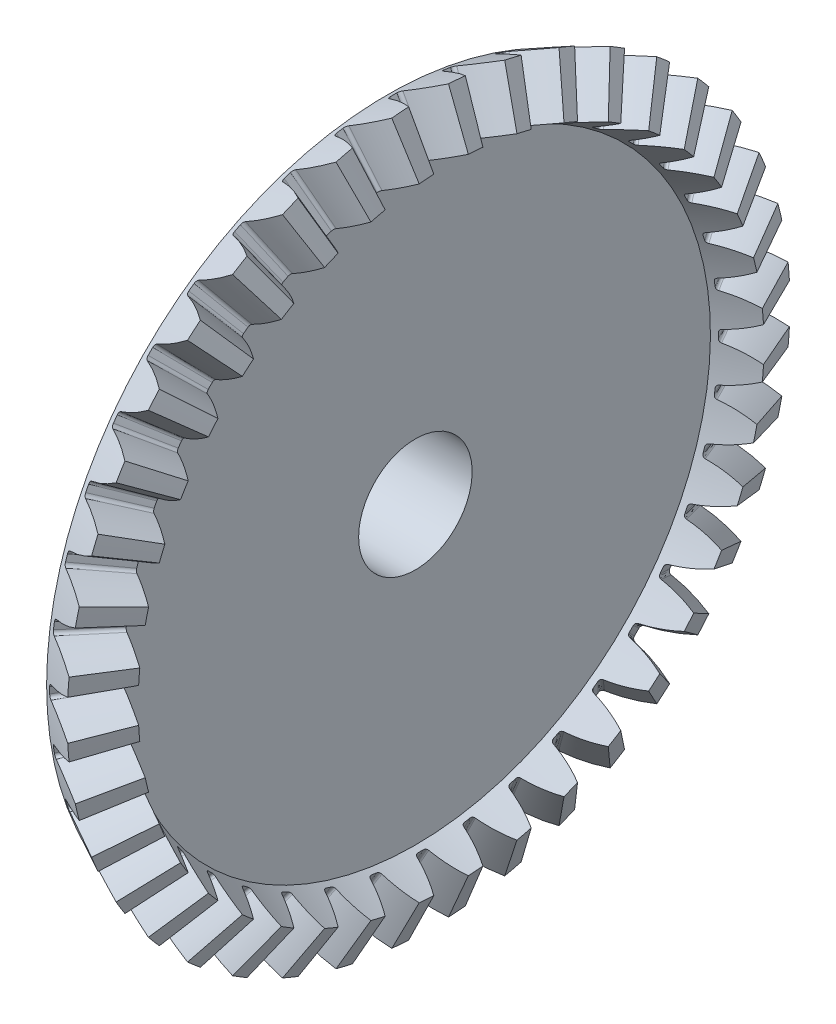
SolidWorks part; units mm, degrees
revolve "Base-Revolve" add sketch "BasProSke" angle 360 about L0 other way angle 4.5
sketch "BasProSke" plane through (0, 0, 0) normal (0, 1, 0) x (1, 0, 0)
  line L0 (-10, 0) -> (60, 0) construction
  line L1 (0, 0) -> (0, 81.0104)
  line L2 (0, 0) -> (6.6607, 0)
  line L3 (6.6607, 0) -> (6.6607, 70.1417)
  line L4 (49.6458, 0) -> (-6.8684, 113.0285) construction
  line L5 (0, 81.0104) -> (9.7926, 85.9067)
  line L6 (49.6458, 0) -> (-8.8085, 126.0029) construction
  line L7 (49.6458, 0) -> (0, 81.0104) construction
  line L8 (9.7926, 85.9067) -> (15.1395, 74.3811)
  line L9 (15.1395, 74.3811) -> (6.6607, 70.1417)
  line L10 (7.3125, 84.6667) -> (-4.6718, 84.6667) construction
  dimension "D4" = 1.678
ref_plane "Plane1" through (0, 0, 0) normal (0, 0, 1) x (1, 0, 0)
ref_plane "Plane2" through (0, 0, 0) normal (0, 1, 0) x (1, 0, 0)
ref_plane "Plane3" through (0, 0, 0) normal (1, 0, 0) x (0, 0, -1)
sketch "HoldingSke" plane through (0, 0, 0) normal (0, 1, 0) x (1, 0, 0)
  line L0 (0, 0) -> (116.7452, -97.9608)
  line L1 (-15, 0) -> (100, 0) construction
  line L2 (0, 0) -> (-75.7593, 24.4387)
  line L3 (0, 0) -> (-11.863, 4.5341)
  line L4 (0, 0) -> (6.6156, 5.5511)
  line L5 (0, 0) -> (-66.6361, -24.8533)
  line L6 (0, 0) -> (-10.5278, -7.1032)
  line L7 (-75.7593, 24.4387) -> (-65.3329, 94.7903)
  line L8 (-76.2, 54.61) -> (-46.2788, 54.61)
  line L9 (-71.009, 38.7566) -> (-53.1078, 45.2721)
  line L10 (-76.2, 71.12) -> (104.1128, 71.12)
  line L11 (0, 0) -> (-12.7, 0)
  line L12 (-76.2, 101.6) -> (-76.0298, 101.6)
  line L13 (24.9733, 27.94) -> (52.9543, 28.2599)
  line L14 (24.9733, 27.94) -> (25.0241, 27.9398)
  line L15 (24.9733, 27.94) -> (100.3916, 29.9584)
  line L16 (-75.7593, 24.4387) -> (45.5619, -19.7186)
  circle A0 centre (0, 0) radius 13.4938
  circle A1 centre (0, 0) radius 19.05
  circle A2 centre (0, 0) radius 19.05
  circle A3 centre (0, 0) radius 13.4938
  dimension "Num_teeth" = 40
  dimension "Pitch_radius" = 180.3128
  dimension "Width" = 12.7
ref_plane "ToothPln" through (4.8963, 83.4586, 0) normal (-0.4472, 0.8944, 0) x (0, 0, -1)
ref_plane "ToothPln2" through (9.9292, -19.8583, 0) normal (-0.4472, 0.8944, 0) x (0, 0, 1)
sketch "TooCutSke" plane through (4.8963, 83.4586, 0) normal (-0.4472, 0.8944, 0) x (0, 0, -1)
  line L2 (0, 81.9653) -> (136.6289, -1654.0695) construction
  line L3 (0, 81.9653) -> (74.2212, -1759.8687) construction
  line L4 (0, -15.621) -> (0, 105.791) construction
  line L6 (-24.765, -5.4742) -> (21.082, -5.4742) construction
  line L7 (6.6429, -2.4404) -> (3.4066, -2.5708) construction
  arc A0 (-5.6568, -7.0434) -> (5.6568, -7.0434) centre (0, 81.9653) ccw
  arc A1 (-0.7735, 3.8429) -> (0.7735, 3.8429) centre (0, 81.9653) ccw
  circle A2 centre (0, 81.9653) radius 84.6667 construction
  circle A3 centre (0, 81.9653) radius 79.5606 construction
  arc A4 (1.6092, 3.1762) -> (0.7735, 3.8429) centre (0.7818, 2.9963) ccw
  arc A5 (1.6092, 3.1762) -> (5.6568, -7.0434) centre (34.7026, 10.3718) ccw
  arc A6 (-5.6568, -7.0434) -> (-1.6092, 3.1762) centre (-34.7026, 10.3718) ccw
  arc A7 (-0.7735, 3.8429) -> (-1.6092, 3.1762) centre (-0.7818, 2.9963) ccw
  ellipse E0 centre (0, 32.9444) end of major axis (85.9067, 32.9444) minor radius 38.4187 construction
sketch "TooCutSke2" plane through (9.9292, -19.8583, 0) normal (-0.4472, 0.8944, 0) x (0, 0, 1)
  line L0 (0, 0) -> (0, 68.072) construction
  line L2 (21.082, 36.229) -> (-20.32, 36.229) construction
  circle A0 centre (0, 44.4046) radius 0.0127
  ellipse E1 centre (0, 0) end of major axis (-81.0104, 0) minor radius 36.229 construction
loft "ToothCut" cut profiles "TooCutSke2", "TooCutSke"
pattern_circular "TeethCuts" count 40 every 9 about axis through (-10, 0, 0) along (1, 0, 0) of "ToothCut"
sketch "HubSke" plane through (0, 0, 0) normal (-1, 0, 0) x (0, 0, 1)
  circle A0 centre (0, 0) radius 19.05
  dimension "Diameter" = 38.1
extrude "Hub" add sketch "HubSke" along normal blind 21.4743
sketch "BorSke" plane through (0, 0, 0) normal (1, 0, 0) x (0, 0, -1)
  circle A0 centre (0, 0) radius 13.4938
  dimension "Diameter" = 26.9875
extrude "Bore" cut sketch "BorSke" along normal mid plane 142.2401
sketch "KeySke" plane through (0, 0, 0) normal (1, 0, 0) x (0, 0, -1)
  line L0 (-3.175, 0) -> (-3.175, 16.4274)
  line L1 (-3.175, 16.4274) -> (3.175, 16.4274)
  line L2 (3.175, 16.4274) -> (3.175, 0)
  line L3 (0, 0) -> (0, 34) construction
  line L4 (-3.175, 0) -> (3.175, 0)
extrude "Keyway" [suppressed] cut sketch "KeySke" along normal mid plane 142.2401
pattern_circular "Keyway2" [suppressed] count 2 every 90 about axis through (-10, 0, 0) along (1, 0, 0)
equation "' \"Pitch@HoldingSke\" = 4"
equation "' \"Num_teeth@HoldingSke\" = 20"
equation "' \"Mating_teeth@HoldingSke\" = 12"
equation "' \"Ap@HoldingSke\" =  20"
equation "' \"Ap@HoldingSke\" = 20"
equation "' \"Width@HoldingSke\" = 0.5"
equation "' \"Hub_dia@HoldingSke\"= 2"
equation "' \"Hub_dia@HoldingSke\" = 2"
equation "' \"Mounting_dist@HoldingSke\" = 3"
equation "' \"Bore@HoldingSke\" = 0.75"
equation "' \"T_dim@HoldingSke\" = 0.85"
equation "' \"Width@KeySke\" = 0.25"
equation "' \"Show_teeth@HoldingSke\" = 100"
equation "' \"Backlash@HoldingSke\" = 0.009"
equation "' \"Addendum_fac@HoldingSke\" = 1.0"
equation "' \"Dedendum_fac@HoldingSke\" = 1.188"
equation "' \"Dedendum_add@HoldingSke\" = 0.002"
equation "' \"Clearance_fac@HoldingSke\" = 0.188"
equation " \"Addendum_fac@HoldingSke\" = 0.54 + 0.46 / (\"Num_teeth@HoldingSke\" /  \"Mating_teeth@HoldingSke\" ) ^ 2"
equation "' \"Addendum_fac@HoldingSke\" = 2 - (0.54 + 0.46 / (\"Mating_teeth@HoldingSke\" /  \"Num_teeth@HoldingSke\" ) ^ 2)"
equation "\"Dedendum_fac@HoldingSke\" = 2.188 - \"Addendum_fac@HoldingSke\""
equation "\"Pitch_rad@BasProSke\" = \"Num_teeth@HoldingSke\" / \"Pitch@HoldingSke\" / 2"
equation "\"Pitch_ang@BasProSke\" = atn(\"Num_teeth@HoldingSke\" / \"Mating_teeth@HoldingSke\") * (180 / 3.14159265)"
equation "\"Addendum@BasProSke\" = \"Addendum_fac@HoldingSke\" / \"Pitch@HoldingSke\""
equation "\"Dedendum_plus@BasProSke\" = (\"Dedendum_fac@HoldingSke\" / \"Pitch@HoldingSke\" + \"Dedendum_add@HoldingSke\") * 1.25"
equation "\"Face_wid@BasProSke\" = \"Width@HoldingSke\""
equation "\"Radius@TooCutSke\" = ((\"Num_teeth@HoldingSke\" + 2 * \"Addendum_fac@HoldingSke\") / \"Pitch@HoldingSke\" ) / 2"
equation "\"Overcut_dia@TooCutSke\" =  1.02 * (\"Num_teeth@HoldingSke\" + 2 * \"Addendum_fac@HoldingSke\") / \"Pitch@HoldingSke\""
equation "\"Pitch_dia@TooCutSke\" = \"Num_teeth@HoldingSke\" / \"Pitch@HoldingSke\""
equation "\"Base_dia@TooCutSke\" = \"Num_teeth@HoldingSke\" / \"Pitch@HoldingSke\" * cos((\"Ap@HoldingSke\"  * 3.14159265 / 180))"
equation "'  \"Root_dia@TooCutSke\" =  (\"Num_teeth@HoldingSke\" + 2) / \"Pitch@HoldingSke\" - 2 * (\"Addendum_fac@HoldingSke\" + \"Dedendum_fac@HoldingSke\") / \"Pitch@HoldingSke\" - \"Dedendum_add@HoldingSke\" * 2"
equation "'  \"Root_dia@TooCutSke\" = (\"Num_teeth@HoldingSke\" + 2) / \"Pitch@HoldingSke\" - 2 * (\"Addendum_fac@HoldingSke\" + \"Dedendum_fac@HoldingSke\") / \"Pitch@HoldingSke\" - \"Dedendum_add@HoldingSke\" * 2"
equation "\"Root_dia@TooCutSke\" =  \"Num_teeth@HoldingSke\" / \"Pitch@HoldingSke\" - 2 * \"Dedendum_fac@HoldingSke\" / \"Pitch@HoldingSke\" - \"Dedendum_add@HoldingSke\" * 2"
equation "\"Half_ang@TooCutSke\" = 180 / \"Num_teeth@HoldingSke\""
equation "\"Half_CT@TooCutSke\" = \"Num_teeth@HoldingSke\" / \"Pitch@HoldingSke\" * sin((3.14159265 / 2 / \"Num_teeth@HoldingSke\")) / 2 - 2 * \"Backlash@HoldingSke\" / 4"
equation "\"Flank_rad@TooCutSke\" = \"Num_teeth@HoldingSke\" / \"Pitch@HoldingSke\" / 5"
equation "\"Root_fillet@TooCutSke\" = \"Clearance_fac@HoldingSke\" / \"Pitch@HoldingSke\" + \"Dedendum_add@HoldingSke\""
equation "\"Offset@ToothPln2\"  = \"Num_teeth@HoldingSke\" / \"Pitch@HoldingSke\" / 2 / sin(atn(\"Num_teeth@HoldingSke\" / \"Mating_teeth@HoldingSke\"))"
equation "\"Dedendum_plus@TooCutSke2\" = \"Dedendum_plus@BasProSke\""
equation "\"MHD@HoldingSke\" = \"Num_teeth@HoldingSke\" / \"Pitch@HoldingSke\" - 2 * \"Dedendum_plus@BasProSke\" * cos(atn(\"Num_teeth@HoldingSke\" / \"Mating_teeth@HoldingSke\"))"
equation "\"MBD@HoldingSke\" = \"Num_teeth@HoldingSke\" / \"Pitch@HoldingSke\" - 2 * \"Dedendum_plus@BasProSke\" * cos(atn(\"Num_teeth@HoldingSke\" / \"Mating_teeth@HoldingSke\")) - 0.002"
equation "\"MnMD@HoldingSke\" =  \"Num_teeth@HoldingSke\" / \"Pitch@HoldingSke\" / 2 / (\"Num_teeth@HoldingSke\" / \"Mating_teeth@HoldingSke\") + \"Dedendum_plus@BasProSke\" * sin(atn(\"Num_teeth@HoldingSke\" / \"Mating_teeth@HoldingSke\"))"
equation "\"OAL@HoldingSke\" = \"MnMD@HoldingSke\""
equation "\"MHD@HoldingSke\" = ((sgn( \"MHD@HoldingSke\" - \"Hub_dia@HoldingSke\" )-1)*( \"MHD@HoldingSke\" - \"Hub_dia@HoldingSke\" ))/-2+ \"Hub_dia@HoldingSke\""
equation "\"MBD@HoldingSke\" = ((sgn( \"MBD@HoldingSke\" - \"Bore@HoldingSke\" )-1)*( \"MBD@HoldingSke\" - \"Bore@HoldingSke\" ))/-2+ \"Bore@HoldingSke\""
equation "\"Face_wid@BasProSke\" = ((sgn( \"Face_wid@BasProSke\" - \"Offset@ToothPln2\" * 0.9)-1)*( \"Face_wid@BasProSke\" - \"Offset@ToothPln2\" * 0.9))/-2+ \"Offset@ToothPln2\" * 0.9"
equation "\"OAL@HoldingSke\" = ((sgn( \"OAL@HoldingSke\" - \"Mounting_dist@HoldingSke\" )+1)*( \"OAL@HoldingSke\" - \"Mounting_dist@HoldingSke\" ))/2 + \"Mounting_dist@HoldingSke\" + 0.000002"
equation "\"Num_teeth@TeethCuts\" = int( \"Show_teeth@HoldingSke\" ) + 1"
equation "\"Num_teeth@TeethCuts\" = ((sgn( \"Num_teeth@TeethCuts\" - \"Num_teeth@HoldingSke\" )-1)*( \"Num_teeth@TeethCuts\" - \"Num_teeth@HoldingSke\" ))/-2+ \"Num_teeth@HoldingSke\""
equation "\"Num_teeth@TeethCuts\" = ((sgn( \"Num_teeth@TeethCuts\" - 2.0)+1)*( \"Num_teeth@TeethCuts\" - 2.0))/2 +2.0"
equation "\"Angle@TeethCuts\" = 360.0 / \"Num_teeth@HoldingSke\""
equation "\"Diameter@HubSke\" = \"MHD@HoldingSke\""
equation "\"Length@Hub\" = \"OAL@HoldingSke\" - \"MnMD@HoldingSke\" + 0.000002"
equation "\"Diameter@BorSke\" = \"MBD@HoldingSke\""
equation "\"D1@Bore\" = \"OAL@HoldingSke\" * 2.0"
equation "\"D1@Keyway\" = \"OAL@HoldingSke\" * 2.0"
equation "\"Offset@KeySke\" = \"T_dim@HoldingSke\" - \"MBD@HoldingSke\" / 2.0"
